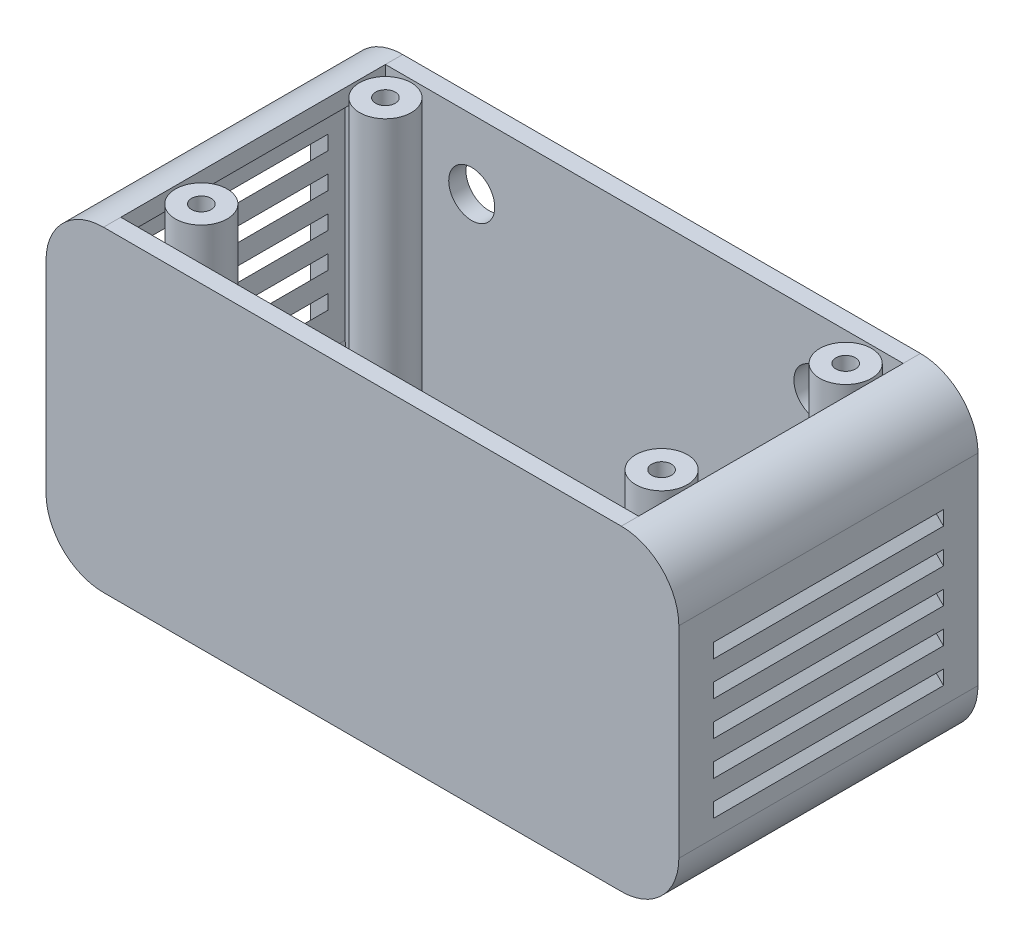
SolidWorks part; units mm, degrees
material "ABS"
ref_plane "Front Plane" through (0, 0, 0) normal (0, 0, 1) x (1, 0, 0)
ref_plane "Top Plane" through (0, 0, 0) normal (0, 1, 0) x (1, 0, 0)
ref_plane "Right Plane" through (0, 0, 0) normal (1, 0, 0) x (0, 0, -1)
sketch "Sketch1" plane through (0, 0, 0) normal (0, 0, 1) x (1, 0, 0)
  line L0 (-45, -55) -> (45, -55)
  line L1 (55, -45) -> (55, -10)
  line L2 (45, 0) -> (-45, 0)
  line L3 (-55, -10) -> (-55, -45)
  arc A0 (45, -55) -> (55, -45) centre (45, -45) ccw
  arc A1 (55, -10) -> (45, 0) centre (45, -10) ccw
  arc A2 (-45, 0) -> (-55, -10) centre (-45, -10) ccw
  arc A3 (-55, -45) -> (-45, -55) centre (-45, -45) ccw
extrude "Boss-Extrude1" add sketch "Sketch1" along normal blind 52
shell "Shell1" thickness 3 removed face at (0, 0, 26)
sketch "Sketch2" plane through (0, 0, 0) normal (0, 1, 0) x (1, 0, 0)
  circle A0 centre (-40, -8) radius 4.5
  circle A1 centre (40, -8) radius 4.5
  circle A2 centre (-40, -40) radius 4.5
  circle A3 centre (40, -40) radius 4.5
extrude "Boss-Extrude2" add sketch "Sketch2" against normal blind 52
sketch "Sketch3" plane through (0, -55, 0) normal (0, -1, 0) x (1, 0, 0)
  circle A0 centre (-40, 8) radius 3.25
  circle A1 centre (40, 8) radius 3.25
  circle A2 centre (-40, 40) radius 3.25
  circle A3 centre (40, 40) radius 3.25
extrude "Cut-Extrude1" cut sketch "Sketch3" against normal blind 49
sketch "Sketch4" plane through (0, -6, 0) normal (0, -1, 0) x (1, 0, 0)
  circle A0 centre (-40, 8) radius 1.7
  circle A1 centre (40, 8) radius 1.7
  circle A2 centre (-40, 40) radius 1.7
  circle A3 centre (40, 40) radius 1.7
extrude "Cut-Extrude2" cut sketch "Sketch4" against normal through all
ref_plane "Plane1" through (0, 0, 26) normal (0, 0, 1) x (1, 0, 0)
sketch "Sketch5" plane through (0, 0, 26) normal (0, 0, 1) x (1, 0, 0)
  line L0 (-51, -14) -> (-51, -11.5)
  line L1 (-51, -11.5) -> (-55.5, -16)
  line L2 (-55.5, -16) -> (-55.5, -18.5)
  line L3 (-55.5, -18.5) -> (-51, -14)
  line L4 (51, -14) -> (51, -11.5)
  line L5 (51, -11.5) -> (55.5, -16)
  line L6 (55.5, -16) -> (55.5, -18.5)
  line L7 (55.5, -18.5) -> (51, -14)
  line L8 (-51, -20) -> (-51, -17.5)
  line L9 (-51, -17.5) -> (-55.5, -22)
  line L10 (-55.5, -22) -> (-55.5, -24.5)
  line L11 (-55.5, -24.5) -> (-51, -20)
  line L12 (51, -20) -> (51, -17.5)
  line L13 (51, -17.5) -> (55.5, -22)
  line L14 (55.5, -22) -> (55.5, -24.5)
  line L15 (55.5, -24.5) -> (51, -20)
  line L16 (-51, -26) -> (-51, -23.5)
  line L17 (-51, -23.5) -> (-55.5, -28)
  line L18 (-55.5, -28) -> (-55.5, -30.5)
  line L19 (-55.5, -30.5) -> (-51, -26)
  line L20 (51, -26) -> (51, -23.5)
  line L21 (51, -23.5) -> (55.5, -28)
  line L22 (55.5, -28) -> (55.5, -30.5)
  line L23 (55.5, -30.5) -> (51, -26)
  line L24 (-51, -32) -> (-51, -29.5)
  line L25 (-51, -29.5) -> (-55.5, -34)
  line L26 (-55.5, -34) -> (-55.5, -36.5)
  line L27 (-55.5, -36.5) -> (-51, -32)
  line L28 (51, -32) -> (51, -29.5)
  line L29 (51, -29.5) -> (55.5, -34)
  line L30 (55.5, -34) -> (55.5, -36.5)
  line L31 (55.5, -36.5) -> (51, -32)
  line L32 (-51, -38) -> (-51, -35.5)
  line L33 (-51, -35.5) -> (-55.5, -40)
  line L34 (-55.5, -40) -> (-55.5, -42.5)
  line L35 (-55.5, -42.5) -> (-51, -38)
  line L36 (51, -38) -> (51, -35.5)
  line L37 (51, -35.5) -> (55.5, -40)
  line L38 (55.5, -40) -> (55.5, -42.5)
  line L39 (55.5, -42.5) -> (51, -38)
extrude "Cut-Extrude3" cut sketch "Sketch5" against normal blind 20 and the other way blind 20
sketch "Sketch6" plane through (0, -55, 0) normal (0, -1, 0) x (1, 0, 0)
  line L0 (-33, 12) -> (-33, 40) construction
  line L1 (-34.5, 12) -> (-34.5, 40)
  line L2 (-31.5, 12) -> (-31.5, 40)
  line L3 (-27, 12) -> (-27, 40) construction
  line L4 (-28.5, 12) -> (-28.5, 40)
  line L5 (-25.5, 12) -> (-25.5, 40)
  line L6 (-21, 12) -> (-21, 40) construction
  line L7 (-22.5, 12) -> (-22.5, 40)
  line L8 (-19.5, 12) -> (-19.5, 40)
  line L9 (-15, 12) -> (-15, 40) construction
  line L10 (-16.5, 12) -> (-16.5, 40)
  line L11 (-13.5, 12) -> (-13.5, 40)
  line L12 (-9, 12) -> (-9, 40) construction
  line L13 (-10.5, 12) -> (-10.5, 40)
  line L14 (-7.5, 12) -> (-7.5, 40)
  line L15 (-3, 12) -> (-3, 40) construction
  line L16 (-4.5, 12) -> (-4.5, 40)
  line L17 (-1.5, 12) -> (-1.5, 40)
  line L18 (3, 12) -> (3, 40) construction
  line L19 (1.5, 12) -> (1.5, 40)
  line L20 (4.5, 12) -> (4.5, 40)
  line L21 (9, 12) -> (9, 40) construction
  line L22 (7.5, 12) -> (7.5, 40)
  line L23 (10.5, 12) -> (10.5, 40)
  line L24 (15, 12) -> (15, 40) construction
  line L25 (13.5, 12) -> (13.5, 40)
  line L26 (16.5, 12) -> (16.5, 40)
  line L27 (21, 12) -> (21, 40) construction
  line L28 (19.5, 12) -> (19.5, 40)
  line L29 (22.5, 12) -> (22.5, 40)
  arc A0 (-34.5, 12) -> (-31.5, 12) centre (-33, 12) ccw
  arc A1 (-31.5, 40) -> (-34.5, 40) centre (-33, 40) ccw
  arc A2 (-28.5, 12) -> (-25.5, 12) centre (-27, 12) ccw
  arc A3 (-25.5, 40) -> (-28.5, 40) centre (-27, 40) ccw
  arc A4 (-22.5, 12) -> (-19.5, 12) centre (-21, 12) ccw
  arc A5 (-19.5, 40) -> (-22.5, 40) centre (-21, 40) ccw
  arc A6 (-16.5, 12) -> (-13.5, 12) centre (-15, 12) ccw
  arc A7 (-13.5, 40) -> (-16.5, 40) centre (-15, 40) ccw
  arc A8 (-10.5, 12) -> (-7.5, 12) centre (-9, 12) ccw
  arc A9 (-7.5, 40) -> (-10.5, 40) centre (-9, 40) ccw
  arc A10 (-4.5, 12) -> (-1.5, 12) centre (-3, 12) ccw
  arc A11 (-1.5, 40) -> (-4.5, 40) centre (-3, 40) ccw
  arc A12 (1.5, 12) -> (4.5, 12) centre (3, 12) ccw
  arc A13 (4.5, 40) -> (1.5, 40) centre (3, 40) ccw
  arc A14 (7.5, 12) -> (10.5, 12) centre (9, 12) ccw
  arc A15 (10.5, 40) -> (7.5, 40) centre (9, 40) ccw
  arc A16 (13.5, 12) -> (16.5, 12) centre (15, 12) ccw
  arc A17 (16.5, 40) -> (13.5, 40) centre (15, 40) ccw
  arc A18 (19.5, 12) -> (22.5, 12) centre (21, 12) ccw
  arc A19 (22.5, 40) -> (19.5, 40) centre (21, 40) ccw
  point P2 (-33, 26)
  point P7 (-27, 26)
  point P14 (-21, 26)
  point P21 (-15, 26)
  point P28 (-9, 26)
  point P35 (-3, 26)
  point P42 (3, 26)
  point P49 (9, 26)
  point P56 (15, 26)
  point P63 (21, 26)
  point P70 (0, 0)
extrude "Cut-Extrude4" cut sketch "Sketch6" against normal blind 3.5
sketch "Sketch7" plane through (0, 0, 0) normal (0, 0, -1) x (-1, 0, 0)
  circle A0 centre (30, -12) radius 4
  circle A1 centre (-30, -12) radius 4
extrude "Cut-Extrude5" cut sketch "Sketch7" against normal blind 3.5
sketch "Sketch8" plane through (0, -52, 0) normal (0, 1, 0) x (1, 0, 0)
  line L0 (-30.25, -26) -> (30.25, -26) construction
  line L1 (27, -44.5) -> (33, -44.5)
  line L2 (27, -44.5) -> (27, -7.5)
  line L3 (27, -7.5) -> (33, -7.5)
  line L4 (33, -44.5) -> (33, -7.5)
  line L5 (27, -44.5) -> (33, -7.5) construction
  line L6 (27, -7.5) -> (33, -44.5) construction
  point P0 (30, -26)
extrude "Boss-Extrude3" add sketch "Sketch8" along normal blind 8
sketch "Sketch9" plane through (0, -44, 0) normal (0, 1, 0) x (1, 0, 0)
  line L0 (-30.25, -26) -> (30.25, -26) construction
  line L1 (29.05, -42.8) -> (30.95, -42.8)
  line L2 (29.05, -42.8) -> (29.05, -9.2)
  line L3 (29.05, -9.2) -> (30.95, -9.2)
  line L4 (30.95, -42.8) -> (30.95, -9.2)
  line L5 (29.05, -42.8) -> (30.95, -9.2) construction
  line L6 (29.05, -9.2) -> (30.95, -42.8) construction
  point P0 (30, -26)
extrude "Cut-Extrude6" cut sketch "Sketch9" against normal blind 6
sketch "Sketch10" plane through (0, -52, 0) normal (0, 1, 0) x (1, 0, 0)
  circle A0 centre (-29, -13) radius 3
  circle A1 centre (-29, -39) radius 3
  circle A2 centre (13, -13) radius 3
  circle A3 centre (13, -39) radius 3
extrude "Boss-Extrude4" add sketch "Sketch10" along normal blind 8
